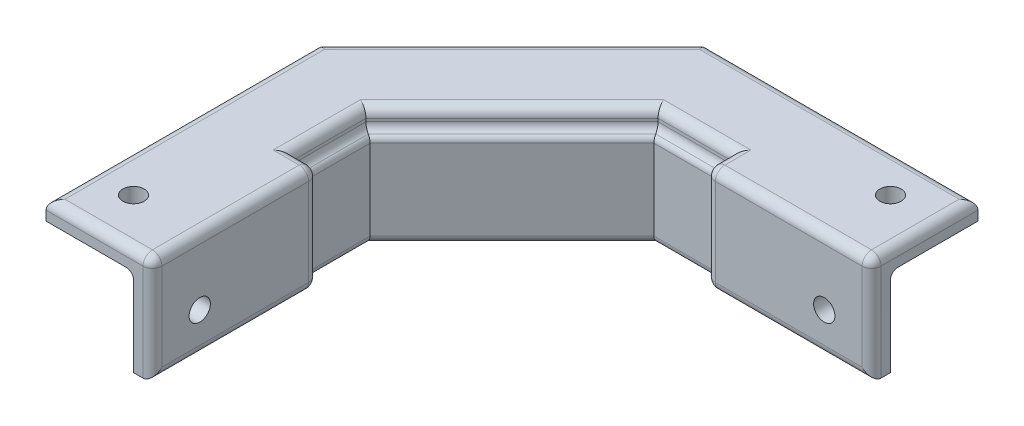
SolidWorks part; units mm, degrees
ref_plane "Front Plane" through (0, 0, 0) normal (0, 0, 1) x (1, 0, 0)
ref_plane "Top Plane" through (0, 0, 0) normal (0, 1, 0) x (1, 0, 0)
ref_plane "Right Plane" through (0, 0, 0) normal (1, 0, 0) x (0, 0, -1)
sketch "Sketch1" plane through (0, 0, 0) normal (0, 1, 0) x (1, 0, 0)
  line L0 (20, -80) -> (20, -50)
  line L1 (41.7157, 0) -> (80, 0)
  line L2 (0, -41.7157) -> (0, -80)
  line L3 (0, -80) -> (20, -80)
  line L4 (80, 0) -> (80, -20)
  line L5 (20, -50) -> (50, -20)
  line L6 (50, -20) -> (80, -20)
  line L7 (0, -41.7157) -> (41.7157, 0)
  dimension "D3" = 20
  dimension "D4" = 20
  dimension "D5" = 45
  dimension "D6" = 30
  dimension "D7" = 20
extrude "Boss-Extrude1" add sketch "Sketch1" along normal blind 20
fillet "Fillet1" radius 1.5 12 edges at (0, 0, 60.8579) (20.8579, 0, 20.8579) (60.8579, 0, 0) (60.8579, 20, 0) (20.8579, 20, 20.8579) (0, 20, 60.8579) (20, 0, 65) (35, 0, 35) (65, 0, 20) (65, 20, 20) (35, 20, 35) (20, 20, 65)
sketch "Sketch2" plane through (0, 0, 20) normal (0, 0, 1) x (1, 0, 0)
  line L5 (50, 1.5) -> (80, 1.5) construction
  line L6 (65, 1.5) -> (100, 1.5)
  line L7 (65, 1.5) -> (65, 18.5)
  line L8 (65, 18.5) -> (100, 18.5)
  line L9 (100, 1.5) -> (100, 18.5)
  line L10 (80, 18.5) -> (50, 18.5) construction
  line L11 (80, 0) -> (80, 1.5) construction
  line L12 (80, 18.5) -> (80, 1.5) construction
  circle A0 centre (90, 10) radius 2.25
  point P10 (80, 0.75)
  dimension "D2" = 10
  dimension "D3" = 4.5
  dimension "D1" = 20
extrude "Boss-Extrude2" add sketch "Sketch2" along normal blind 4
sketch "Sketch3" plane through (20, 0, 0) normal (1, 0, 0) x (0, 0, -1)
  line L0 (-80, 1.5) -> (-50, 1.5) construction
  line L1 (-65, 1.5) -> (-100, 1.5)
  line L2 (-65, 1.5) -> (-65, 18.5)
  line L3 (-65, 18.5) -> (-100, 18.5)
  line L4 (-100, 1.5) -> (-100, 18.5)
  line L5 (-50, 18.5) -> (-80, 18.5) construction
  line L6 (-80, 18.5) -> (-80, 1.5) construction
  circle A0 centre (-90, 10) radius 2.25
  dimension "D2" = 10
  dimension "D3" = 4.5
  dimension "D1" = 20
  dimension "D4" = 15
extrude "Boss-Extrude3" add sketch "Sketch3" along normal blind 4
sketch "Sketch4" plane through (0, 20, 0) normal (0, 1, 0) x (1, 0, 0)
  line L3 (18.5, -100) -> (1.5, -100)
  line L6 (1.5, -80) -> (18.5, -80) construction
  line L11 (100, -18.5) -> (100, -1.5)
  line L12 (80, -18.5) -> (80, -1.5) construction
  line L15 (18.5, -100) -> (18.5, -65)
  line L16 (18.5, -80) -> (18.5, -49.3787) construction
  line L17 (18.5, -65) -> (1.5, -65)
  line L18 (1.5, -42.337) -> (1.5, -80) construction
  line L19 (1.5, -65) -> (1.5, -100)
  line L20 (100, -1.5) -> (65, -1.5)
  line L21 (80, -1.5) -> (42.337, -1.5) construction
  line L22 (65, -1.5) -> (65, -18.5)
  line L23 (49.3787, -18.5) -> (80, -18.5) construction
  line L24 (65, -18.5) -> (100, -18.5)
  circle A0 centre (10, -90) radius 2.25
  circle A1 centre (90, -10) radius 2.25
  dimension "D2" = 10
  dimension "D3" = 4.5
  dimension "D4" = 15
  dimension "D5" = 15
  dimension "D7" = 10
  dimension "D9" = 4.5
  dimension "D1" = 20
  dimension "D6" = 20
extrude "Boss-Extrude4" add sketch "Sketch4" along normal blind 4
sketch "Sketch5" plane through (0, 0, 100) normal (0, 0, 1) x (1, 0, 0)
  line L0 (20, 18.5) -> (24, 18.5)
  line L2 (24, 18.5) -> (24, 24)
  line L5 (24, 24) -> (18.5, 24)
  line L6 (18.5, 24) -> (18.5, 20)
  arc A0 (20, 18.5) -> (18.5, 20) centre (18.5, 18.5) ccw
extrude "Boss-Extrude5" add sketch "Sketch5" against normal up to surface (35 mm away) up to face at (22, 10, 65)
sketch "Sketch6" plane through (100, 0, 0) normal (1, 0, 0) x (0, 0, -1)
  line L1 (-18.5, 24) -> (-24, 24)
  line L2 (-18.5, 24) -> (-18.5, 20)
  line L3 (-20, 18.5) -> (-24, 18.5)
  line L4 (-24, 24) -> (-24, 18.5)
  arc A0 (-18.5, 20) -> (-20, 18.5) centre (-18.5, 18.5) ccw
extrude "Boss-Extrude6" add sketch "Sketch6" against normal up to surface (35 mm away) up to face at (65, 10, 22)
sketch "Sketch7" plane through (0, 24, 0) normal (0, 1, 0) x (1, 0, 0)
  line L0 (65, -1.5) -> (42.337, -1.5)
  line L1 (42.337, -1.5) -> (1.5, -42.337)
  line L2 (1.5, -42.337) -> (1.5, -65)
  line L3 (1.5, -65) -> (18.5, -65)
  line L4 (18.5, -65) -> (18.5, -49.3787)
  line L5 (18.5, -49.3787) -> (49.3787, -18.5)
  line L6 (49.3787, -18.5) -> (65, -18.5)
  line L7 (65, -18.5) -> (65, -1.5)
extrude "Boss-Extrude7" add sketch "Sketch7" against normal through all
fillet "Fillet4" radius 2 20 edges at (65, 1.5, 22) (24, 12.75, 65) (22, 1.5, 65) (24, 1.5, 82.5) (24, 12.75, 100) (12.75, 24, 100) (24, 24, 82.5) (21.25, 24, 65) (18.5, 24, 57.1893) (100, 12.75, 24) (100, 24, 12.75) (65, 24, 21.25) (65, 12.75, 24) (82.5, 1.5, 24) (82.5, 24, 24) (71.1685, 24, 1.5) (57.1893, 24, 18.5) (33.9393, 24, 33.9393) (21.9185, 24, 21.9185) (1.5, 24, 71.1685)
fillet "Fillet5" radius 2 14 edges at (20, 1.5, 73.5) (20, 2.0858, 65.5858) (19.5607, 19.5607, 65) (65, 19.5607, 19.5607) (73.5, 1.5, 20) (65.5858, 2.0858, 20) (61.1685, 20, 1.5) (21.9185, 20, 21.9185) (1.5, 20, 61.1685) (20, 11, 65) (65, 11, 20) (57.1893, 20, 18.5) (33.9393, 20, 33.9393) (18.5, 20, 57.1893)
sketch "Sketch8" plane through (100, 0, 0) normal (1, 0, 0) x (0, 0, -1)
  line L0 (-22, 20) -> (-24, 20)
  line L1 (-24, 20) -> (-24, 27.9584)
  line L4 (-20, 20) -> (-22, 20)
  line L6 (0, 0) -> (6.2305, 18.5)
  line L7 (6.2305, 18.5) -> (-4.844, 27.9584)
  line L9 (-22, 22) -> (-22, 1.5) construction
  line L11 (-22, 27.9584) -> (-4.844, 27.9584)
  line L12 (-24, 27.9584) -> (-22, 27.9584)
  arc A1 (0, 0) -> (-20, 20) centre (-20, 0) ccw
  dimension "D1" = 2
extrude "Cut-Extrude1" [suppressed] cut sketch "Sketch8" against normal through all
fillet "Fillet6" [suppressed] radius 2
fillet "Fillet7" [suppressed] radius 2
